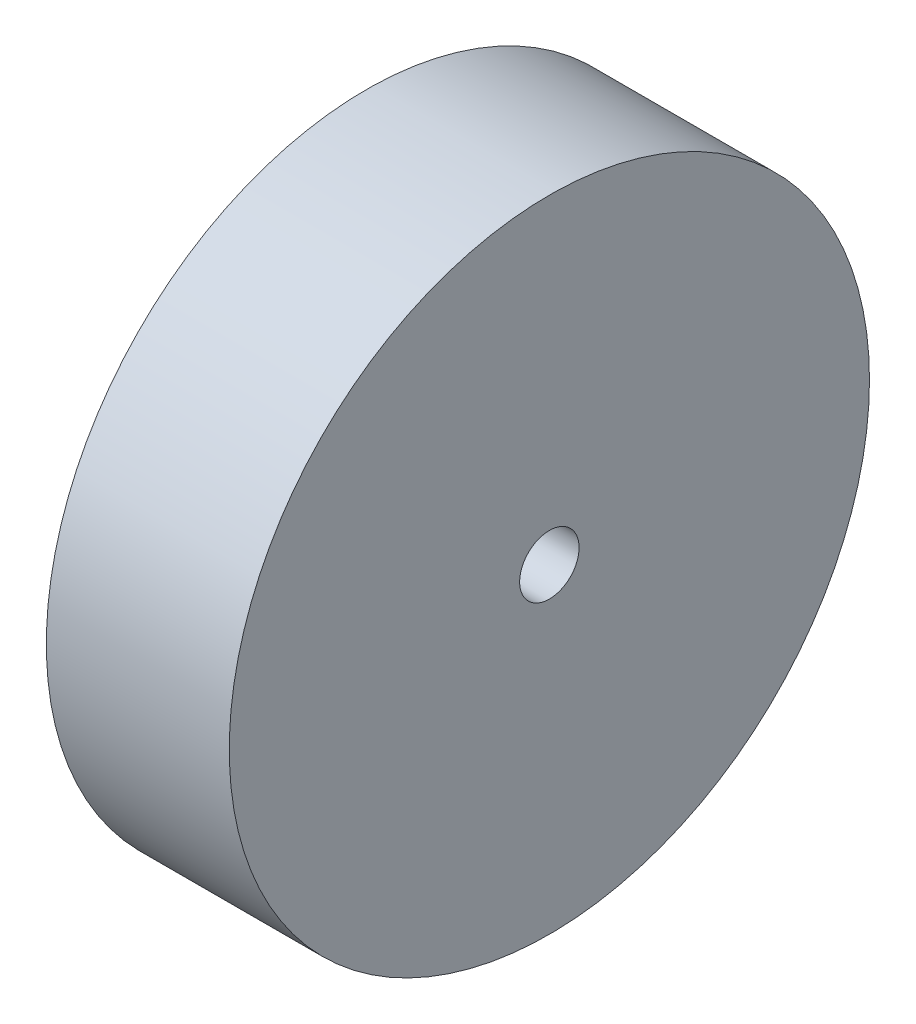
SolidWorks part; units mm, degrees
ref_plane "정면" through (0, 0, 0) normal (0, 0, 1) x (1, 0, 0)
ref_plane "윗면" through (0, 0, 0) normal (0, 1, 0) x (1, 0, 0)
ref_plane "우측면" through (0, 0, 0) normal (1, 0, 0) x (0, 0, -1)
ref_plane "평면4" through (106.6645, 0, 0) normal (1, 0, 0) x (0, 0, -1)
sketch "스케치1" plane through (106.6645, 0, 0) normal (1, 0, 0) x (0, 0, -1)
  circle A0 centre (-20.0599, 49.9391) radius 35
  circle A1 centre (-20.0599, 49.9391) radius 2.75
  circle A2 centre (-20.0599, 49.9391) radius 2.75 construction
  circle A3 centre (-20.0599, 49.9391) radius 3.25
  dimension "D2" = 70
  dimension "D3" = 0.5
  dimension "D1" = 0
extrude "보스-돌출1" add sketch "스케치1" along normal blind 10 and the other way blind 10
